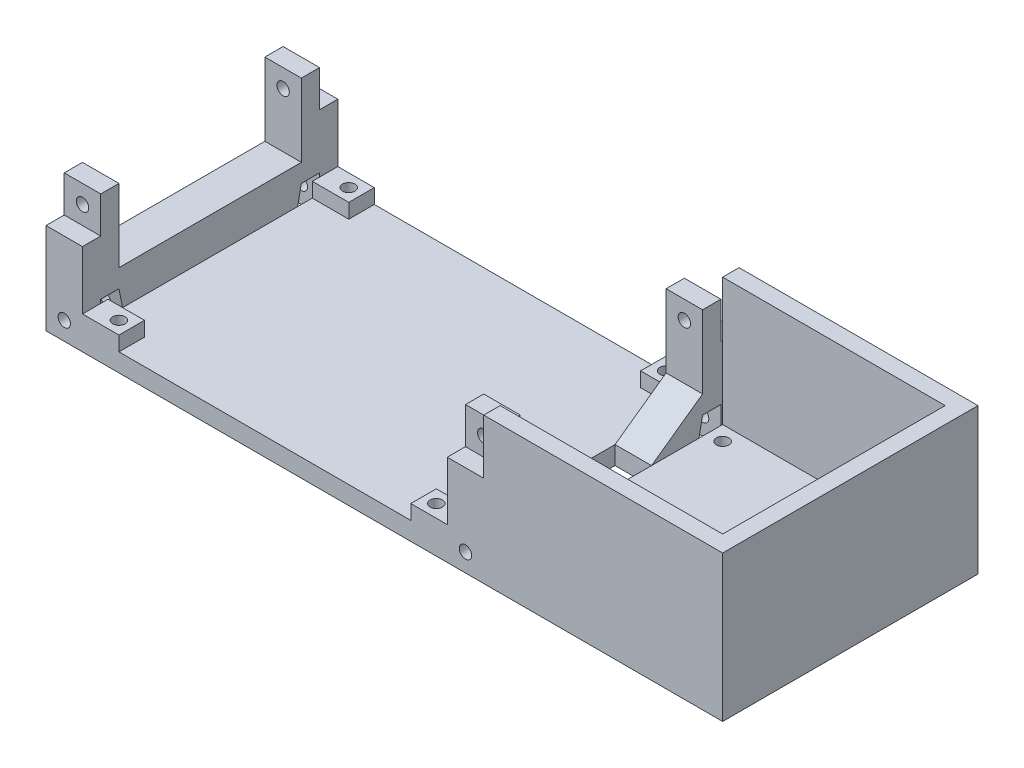
SolidWorks part; units mm, degrees
ref_plane "Front Plane" through (0, 0, 0) normal (0, 0, 1) x (1, 0, 0)
ref_plane "Top Plane" through (0, 0, 0) normal (0, 1, 0) x (1, 0, 0)
ref_plane "Right Plane" through (0, 0, 0) normal (1, 0, 0) x (0, 0, -1)
sketch "Sketch1" plane through (0, 0, 0) normal (0, 1, 0) x (1, 0, 0)
  line L1 (-60, -35) -> (60, -35)
  line L2 (-60, -35) -> (-60, 35)
  line L3 (-60, 35) -> (60, 35)
  line L4 (60, -35) -> (60, 35)
  line L5 (-60, -35) -> (60, 35) construction
  line L6 (-60, 35) -> (60, -35) construction
  point P0 (0, 0)
  dimension "D1" = 120
  dimension "D2" = 70
extrude "Boss-Extrude1" add sketch "Sketch1" along normal blind 5
sketch "Sketch4" plane through (0, 5, 0) normal (0, 1, 0) x (1, 0, 0)
  line L1 (-60, -35) -> (-50, -35)
  line L2 (-60, -35) -> (-60, -25)
  line L3 (-60, -25) -> (-50, -25)
  line L4 (-50, -35) -> (-50, -25)
  line L5 (-60, 35) -> (-50, 35)
  line L6 (-60, 35) -> (-60, 25)
  line L7 (-60, 25) -> (-50, 25)
  line L8 (-50, 35) -> (-50, 25)
  line L9 (60, -35) -> (50, -35)
  line L10 (60, -35) -> (60, -25)
  line L11 (60, -25) -> (50, -25)
  line L12 (50, -35) -> (50, -25)
  line L13 (60, 35) -> (50, 35)
  line L14 (60, 35) -> (60, 25)
  line L15 (60, 25) -> (50, 25)
  line L16 (50, 35) -> (50, 25)
  dimension "D1" = 10
  dimension "D2" = 10
extrude "Boss-Extrude2" add sketch "Sketch4" along normal blind 30
sketch "Sketch5" plane through (0, 0, 0) normal (0, -1, 0) x (1, 0, 0)
  line L0 (-60, -35) -> (-60, 35) construction
  line L1 (-60, -30) -> (-50, -30)
  line L2 (-60, -30) -> (-60, -25)
  line L3 (-60, -25) -> (-50, -25)
  line L4 (-50, -30) -> (-50, -25)
  line L5 (60, 35) -> (60, -35) construction
  line L6 (-60, 30) -> (-50, 30)
  line L7 (-60, 30) -> (-60, 25)
  line L8 (-60, 25) -> (-50, 25)
  line L9 (-50, 30) -> (-50, 25)
  line L10 (60, 30) -> (50, 30)
  line L11 (60, 30) -> (60, 25)
  line L12 (60, 25) -> (50, 25)
  line L13 (50, 30) -> (50, 25)
  line L14 (60, -35) -> (-60, -35) construction
  line L15 (60, -30) -> (50, -30)
  line L16 (60, -30) -> (60, -25)
  line L17 (60, -25) -> (50, -25)
  line L18 (50, -30) -> (50, -25)
  line L19 (-60, 35) -> (60, 35) construction
  dimension "D1" = 10
  dimension "D2" = 5
  dimension "D3" = 5
  dimension "D4" = 5
extrude "Cut-Extrude2" cut sketch "Sketch5" against normal blind 10
sketch "Sketch11" plane through (0, 35, 0) normal (0, 1, 0) x (1, 0, 0)
  line L0 (-50, -35) -> (-50, -25) construction
  line L1 (-60, -35) -> (-50, -35)
  line L2 (-60, -35) -> (-60, -30)
  line L3 (-60, -30) -> (-50, -30)
  line L4 (-50, -35) -> (-50, -30)
  line L5 (60, -35) -> (60, -25) construction
  line L6 (50, -35) -> (60, -35)
  line L7 (50, -35) -> (50, -30)
  line L8 (50, -30) -> (60, -30)
  line L9 (60, -35) -> (60, -30)
  line L10 (60, 25) -> (60, 35) construction
  line L11 (50, 35) -> (60, 35)
  line L12 (50, 35) -> (50, 30)
  line L13 (50, 30) -> (60, 30)
  line L14 (60, 35) -> (60, 30)
  line L15 (-50, 25) -> (-50, 35) construction
  line L16 (-60, 35) -> (-50, 35)
  line L17 (-60, 35) -> (-60, 30)
  line L18 (-60, 30) -> (-50, 30)
  line L19 (-50, 35) -> (-50, 30)
extrude "Cut-Extrude4" cut sketch "Sketch11" against normal blind 10
sketch "Sketch8" plane through (0, 5, 0) normal (0, 1, 0) x (1, 0, 0)
  line L1 (-50, 35) -> (-40, 35)
  line L2 (-50, 35) -> (-50, 28)
  line L3 (-50, 28) -> (-40, 28)
  line L4 (-40, 35) -> (-40, 28)
  line L5 (-50, -35) -> (-40, -35)
  line L6 (-50, -35) -> (-50, -28)
  line L7 (-50, -28) -> (-40, -28)
  line L8 (-40, -35) -> (-40, -28)
  line L9 (50, -35) -> (40, -35)
  line L10 (50, -35) -> (50, -28)
  line L11 (50, -28) -> (40, -28)
  line L12 (40, -35) -> (40, -28)
  line L13 (50, 35) -> (40, 35)
  line L14 (50, 35) -> (50, 28)
  line L15 (50, 28) -> (40, 28)
  line L16 (40, 35) -> (40, 28)
  dimension "D1" = 7
  dimension "D2" = 10
extrude "Boss-Extrude5" add sketch "Sketch8" along normal blind 4
hole_wizard "M3 Clearance Hole2" positions "Sketch10" profile "Sketch9" hole size "M3" standard "ANSI Metric"
sketch "Sketch10" plane through (0, 9, 0) normal (0, 1, 0) x (1, 0, 0)
  line L1 (40, -35) -> (50, -35) construction
  line L2 (-50, -30) -> (-50, -28) construction
  point P0 (-43.5, -31.5)
  point P2 (-43.5, 31.5)
  point P4 (43.5, 31.5)
  point P6 (43.5, -31.5)
  dimension "D1" = 87
  dimension "D2" = 63
  dimension "D3" = 3.5
  dimension "D4" = 6.5
sketch "Sketch9" plane through (-43.5, 9, 31.5) normal (1, 0, 0) x (0, 0, 1)
  line L0 (0, 0) -> (0, 66.0215)
  line L1 (0, 66.0215) -> (1.7, 65)
  line L2 (1.7, 65) -> (1.7, 0)
  line L5 (1.7, 0) -> (0, 0)
  line L10 (0, 66.0215) -> (-1.7, 65) construction
  line L11 (0, -6.35) -> (0, 107.95) construction
  dimension "Hole Dia." = 3.4
  dimension "Hole Depth" = 65
  dimension "Drill Angle" = 118
sketch "Sketch12" plane through (0, 0, 0) normal (0, -1, 0) x (1, 0, 0)
  line L1 (125.5, 35) -> (60, 35)
  line L2 (125.5, 35) -> (125.5, -35)
  line L3 (125.5, -35) -> (60, -35)
  line L4 (60, 35) -> (60, -35)
  line L5 (125.5, 35) -> (60, -35) construction
  line L6 (125.5, -35) -> (60, 35) construction
  line L7 (60, 25) -> (60, -25) construction
  point P0 (92.75, 0)
  dimension "D1" = 65.5
  dimension "D2" = 70
extrude "Boss-Extrude6" add sketch "Sketch12" against normal blind 5
sketch "Sketch13" plane through (0, 5, 0) normal (0, 1, 0) x (1, 0, 0)
  line L1 (60, 35) -> (125.5, 35)
  line L2 (60, 35) -> (60, 30.5)
  line L3 (60, 30.5) -> (121, 30.5)
  line L4 (125.5, -35) -> (125.5, 35)
  line L5 (125.5, 35) -> (125.5, -35) construction
  line L6 (60, -35) -> (125.5, -35)
  line L7 (60, -35) -> (60, -30.5)
  line L8 (60, -30.5) -> (121, -30.5)
  line L11 (121, 30.5) -> (121, -30.5)
  dimension "D1" = 61
  dimension "D2" = 4.5
  dimension "D3" = 4.5
extrude "Boss-Extrude7" add sketch "Sketch13" along normal blind 35
hole_wizard "M3 Clearance Hole3" positions "Sketch15" profile "Sketch14" hole size "M3" standard "ANSI Metric"
sketch "Sketch15" plane through (0, 5, 0) normal (0, 1, 0) x (1, 0, 0)
  line L0 (121, -30.5) -> (60, -30.5) construction
  line L2 (60, -30) -> (60, -25) construction
  point P0 (117, -26.5)
  point P2 (117, 26.5)
  point P4 (64, 26.5)
  point P6 (64, -26.5)
  point P15 (60, -27.5)
  dimension "D1" = 53
  dimension "D2" = 53
  dimension "D3" = 4
  dimension "D4" = 4
sketch "Sketch14" plane through (117, 5, 26.5) normal (1, 0, 0) x (0, 0, 1)
  line L0 (0, 0) -> (0, 66.0215)
  line L1 (0, 66.0215) -> (1.7, 65)
  line L2 (1.7, 65) -> (1.7, 0)
  line L5 (1.7, 0) -> (0, 0)
  line L10 (0, 66.0215) -> (-1.7, 65) construction
  line L11 (0, -6.35) -> (0, 107.95) construction
  dimension "Hole Dia." = 3.4
  dimension "Hole Depth" = 65
  dimension "Drill Angle" = 118
sketch "Sketch24" plane through (0, 5, 0) normal (0, 1, 0) x (1, 0, 0)
  line L1 (-60, 25) -> (-50, 25)
  line L2 (-60, 25) -> (-60, -25)
  line L3 (-60, -25) -> (-50, -25)
  line L4 (-50, 25) -> (-50, -25)
  line L5 (60, -25) -> (50, -25)
  line L6 (60, -25) -> (60, 25)
  line L7 (60, 25) -> (50, 25)
  line L8 (50, -25) -> (50, 25)
extrude "Boss-Extrude10" add sketch "Sketch24" along normal blind 10
sketch "Sketch16" plane through (0, 15, 0) normal (0, 1, 0) x (1, 0, 0)
  line L0 (50, 25) -> (50, -25) construction
  line L1 (60, -11) -> (50, -11)
  line L2 (60, -11) -> (60, 11)
  line L3 (60, 11) -> (50, 11)
  line L4 (50, -11) -> (50, 11)
  line L6 (60, -30) -> (60, -25) construction
  line L9 (60, -25) -> (50, -25) construction
  line L10 (50, 25) -> (60, 25) construction
  dimension "D1" = 14
  dimension "D2" = 14
extrude "Cut-Extrude5" cut sketch "Sketch16" against normal through all
sketch "Sketch22" plane through (0, 0, 35) normal (0, 0, 1) x (1, 0, 0)
  line L0 (-60, 0) -> (125.5, 0) construction
  line L2 (-60, 25) -> (-60, 0) construction
  line L3 (50, 25) -> (50, 9) construction
  circle A0 centre (-55, 5) radius 1.7
  circle A1 centre (55, 5) radius 1.7
  dimension "D3" = 3.4
  dimension "D1" = 5
  dimension "D2" = 5
  dimension "D4" = 5
extrude "Cut-Extrude7" cut sketch "Sketch22" against normal blind 20
chamfer "Chamfer2" distance 14 distance2 10 2 edges at (55, 15, 11) (55, 15, -11) first distance on face at (53.75, 15, 18) first distance on face at (56.25, 15, -18)
sketch "Sketch25" plane through (0, 0, 0) normal (0, -1, 0) x (1, 0, 0)
  line L0 (-60, 25) -> (-50, 25) construction
  line L1 (-57.745, -20) -> (-52.255, -20)
  line L2 (-57.745, -20) -> (-57.745, -17)
  line L3 (-57.745, -17) -> (-52.255, -17)
  line L4 (-52.255, -20) -> (-52.255, -17)
  line L5 (52.255, -20) -> (57.745, -20)
  line L6 (52.255, -20) -> (52.255, -17)
  line L7 (52.255, -17) -> (57.745, -17)
  line L8 (57.745, -20) -> (57.745, -17)
  line L9 (52.255, 20) -> (57.745, 20)
  line L10 (52.255, 20) -> (52.255, 17)
  line L11 (52.255, 17) -> (57.745, 17)
  line L12 (57.745, 20) -> (57.745, 17)
  line L13 (-57.745, 20) -> (-52.255, 20)
  line L14 (-57.745, 20) -> (-57.745, 17)
  line L15 (-57.745, 17) -> (-52.255, 17)
  line L16 (-52.255, 20) -> (-52.255, 17)
  line L17 (-50, -25) -> (-60, -25) construction
  line L18 (-50, -25) -> (-60, -25) construction
  line L23 (55, 25) -> (55, -25) construction
  line L24 (50, 25) -> (60, 25) construction
  line L25 (60, -25) -> (50, -25) construction
  line L26 (-55, 25) -> (-55, -25) construction
  line L27 (-60, 25) -> (-50, 25) construction
  dimension "D1" = 3
  dimension "D2" = 5
  dimension "D3" = 5
  dimension "D4" = 5.49
  dimension "D5" = 2.745
  dimension "D6" = 2.745
extrude "Cut-Extrude8" cut sketch "Sketch25" against normal blind 8
sketch "Sketch26" plane through (0, 0, -35) normal (0, 0, -1) x (-1, 0, 0)
  circle A0 centre (-55, 5) radius 1.7
  circle A1 centre (55, 5) radius 1.7
  circle A2 centre (55, 5) radius 1.7 construction
  circle A3 centre (-55, 5) radius 1.7 construction
extrude "Cut-Extrude9" cut sketch "Sketch26" against normal blind 20
sketch "Sketch27" plane through (0, 0, -30) normal (0, 0, -1) x (-1, 0, 0)
  line L0 (-60, 25) -> (-60, 35) construction
  line L1 (-50, 35) -> (-60, 35) construction
  line L2 (50, 25) -> (50, 35) construction
  circle A0 centre (-55, 30) radius 1.7
  circle A1 centre (55, 30) radius 1.7
  dimension "D3" = 3.4
  dimension "D1" = 5
  dimension "D2" = 5
  dimension "D4" = 5
extrude "Cut-Extrude10" cut sketch "Sketch27" against normal through all
sketch "Sketch28" plane through (-60, 0, 0) normal (-1, 0, 0) x (0, 0, 1)
  line L0 (-25, 10) -> (-23, 0)
  line L1 (-25, 0) -> (25, 0) construction
  line L2 (-23, 0) -> (-25, 0)
  line L3 (-25, 0) -> (-25, 10)
  line L4 (25, 10) -> (23, 0)
  line L5 (23, 0) -> (25, 0)
  line L6 (25, 10) -> (25, 0) construction
  line L7 (25, 0) -> (25, 10)
  dimension "D1" = 2
extrude "Cut-Extrude11" cut sketch "Sketch28" against normal blind 10
pattern_linear "LPattern1" count 2 spacing 110 along (1, 0, 0) of "Cut-Extrude11"
equation "\"D5@Sketch25\"=\"D4@Sketch25\"/2"
equation "\"D6@Sketch25\"=\"D5@Sketch25\""
